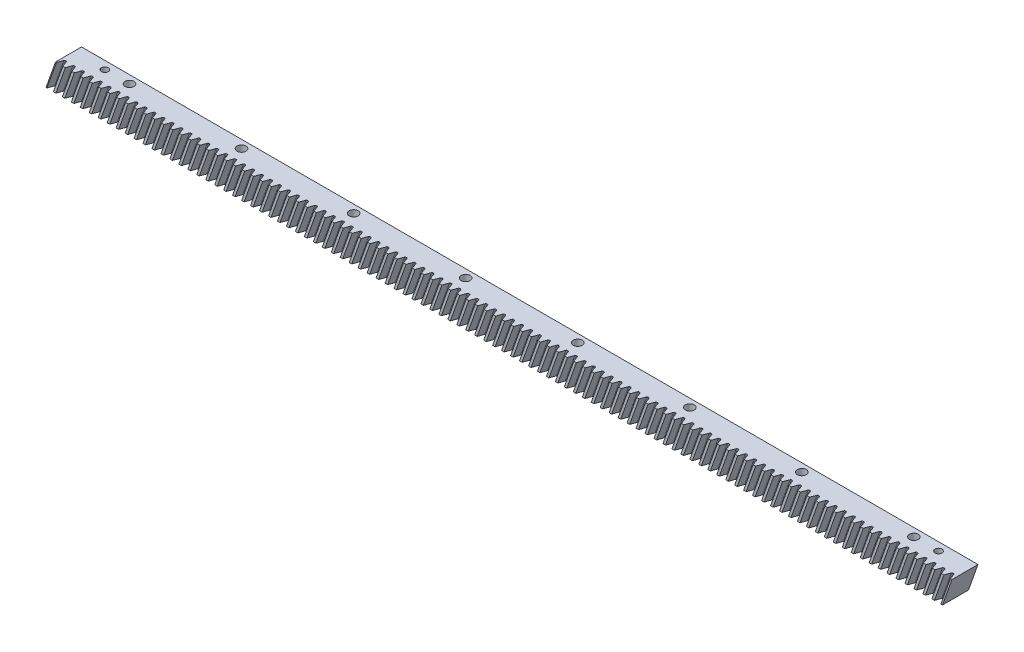
SolidWorks part; units mm, degrees
ref_plane "前视基准面" through (0, 0, 0) normal (0, 0, 1) x (1, 0, 0)
ref_plane "上视基准面" through (0, 0, 0) normal (0, 1, 0) x (1, 0, 0)
ref_plane "右视基准面" through (0, 0, 0) normal (1, 0, 0) x (0, 0, -1)
sketch "草图1" plane through (0, 0, 0) normal (0, 0, 1) x (1, 0, 0)
  line L0 (0, 0) -> (10.6236, 30)
  line L1 (0, 0) -> (1000, 0)
  line L2 (1010.6236, 30) -> (1000, 0)
  line L3 (10.6236, 30) -> (1000, 30)
  line L5 (1000, 30) -> (1010.6236, 30)
  dimension "D1" = 1000
  dimension "D2" = 1000
  dimension "D3" = 30
  dimension "D4" = 109.5
extrude "凸台-拉伸2" add sketch "草图1" along normal blind 29
sketch "草图2" plane through (0, 30, 0) normal (0, 1, 0) x (1, 0, 0)
  line L0 (10.6236, -29) -> (10.6236, 0) construction
  line L1 (1010.6236, 0) -> (10.6236, 0) construction
  circle A0 centre (45.6236, -9) radius 3.85
  dimension "D2" = 7.7
  dimension "D1" = 35
  dimension "D3" = 9
extrude "切除-拉伸1" cut sketch "草图2" against normal up to next
pattern_linear "阵列(线性)1" count 2 spacing 930 along (1, 0, 0) of "切除-拉伸1"
sketch "草图3" plane through (0, 30, 0) normal (0, 1, 0) x (1, 0, 0)
  line L0 (1010.6236, 0) -> (10.6236, 0) construction
  line L1 (10.6236, -29) -> (10.6236, 0) construction
  line L2 (73.1236, 15.076) -> (73.1236, -66.486) construction
  circle A0 centre (73.1236, -9) radius 5
  dimension "D2" = 10
  dimension "D1" = 62.5
  dimension "D3" = 9
extrude "切除-拉伸2" cut sketch "草图3" against normal blind 21
sketch "草图4" plane through (0, 0, 0) normal (0, -1, 0) x (1, 0, 0)
  line L0 (0, 0) -> (1000, 0) construction
  circle A0 centre (73.1236, 9) radius 7.5
  dimension "D1" = 15
  dimension "D2" = 62.5
  dimension "D3" = 9
extrude "切除-拉伸3" cut sketch "草图4" against normal blind 9
pattern_linear "阵列(线性)2" count 8 spacing 125 along (1, 0, 0) of "切除-拉伸2", "切除-拉伸3"
sketch "草图6" plane through (0, 30, 0) normal (0, 1, 0) x (1, 0, 0)
  line L0 (5.1915, -26) -> (49.3828, -26) construction
  line L2 (6.4314, -22.25) -> (25.2757, -22.25) construction
  line L3 (1010.6236, -29) -> (10.6236, -29) construction
  line L5 (11.6236, -29) -> (13.8409, -22.908)
  line L6 (14.7806, -22.25) -> (15.6504, -22.25)
  line L7 (16.5901, -22.908) -> (18.8074, -29)
  line L8 (18.8074, -29) -> (11.6236, -29)
  arc A0 (14.7806, -22.25) -> (13.8409, -22.908) centre (14.7806, -23.25) ccw
  arc A1 (15.6504, -22.25) -> (16.5901, -22.908) centre (15.6504, -23.25) cw
  point P8 (17.7155, -26)
  point P11 (12.7155, -26)
  point P15 (14.0804, -22.25)
  point P18 (16.3506, -22.25)
  dimension "D7" = 1
  dimension "D1" = 3
  dimension "D2" = 3.75
  dimension "D3" = 70
  dimension "D4" = 70
  dimension "D5" = 1
  dimension "D6" = 5
extrude "切除-拉伸4" cut sketch "草图6" along direction (-0.3338, -0.9426, 0) on the side against the normal up to next (30 mm away)
pattern_linear "阵列(线性)3" count 100 spacing 10 along (1, 0, 0) of "切除-拉伸4"
